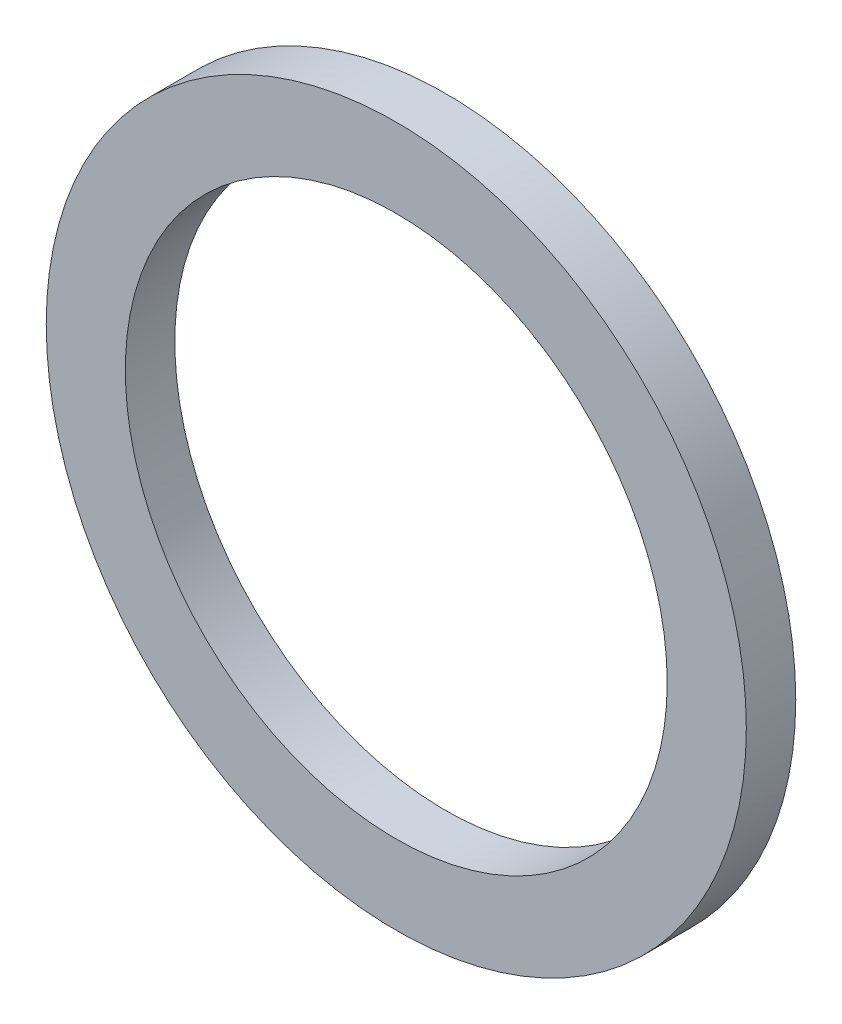
SolidWorks part; units mm, degrees
material "Plain Carbon Steel"
ref_plane "Front Plane" through (0, 0, 0) normal (0, 0, 1) x (1, 0, 0)
ref_plane "Top Plane" through (0, 0, 0) normal (0, 1, 0) x (1, 0, 0)
ref_plane "Right Plane" through (0, 0, 0) normal (1, 0, 0) x (0, 0, -1)
sketch "Sketch1" plane through (0, 0, 0) normal (0, 0, 1) x (1, 0, 0)
  circle A0 centre (0, 0) radius 22.479
  circle A1 centre (0, 0) radius 17.399
  dimension "D1" = 44.958
  dimension "D2" = 5.08
extrude "Boss-Extrude1" add sketch "Sketch1" along normal blind 3.175
